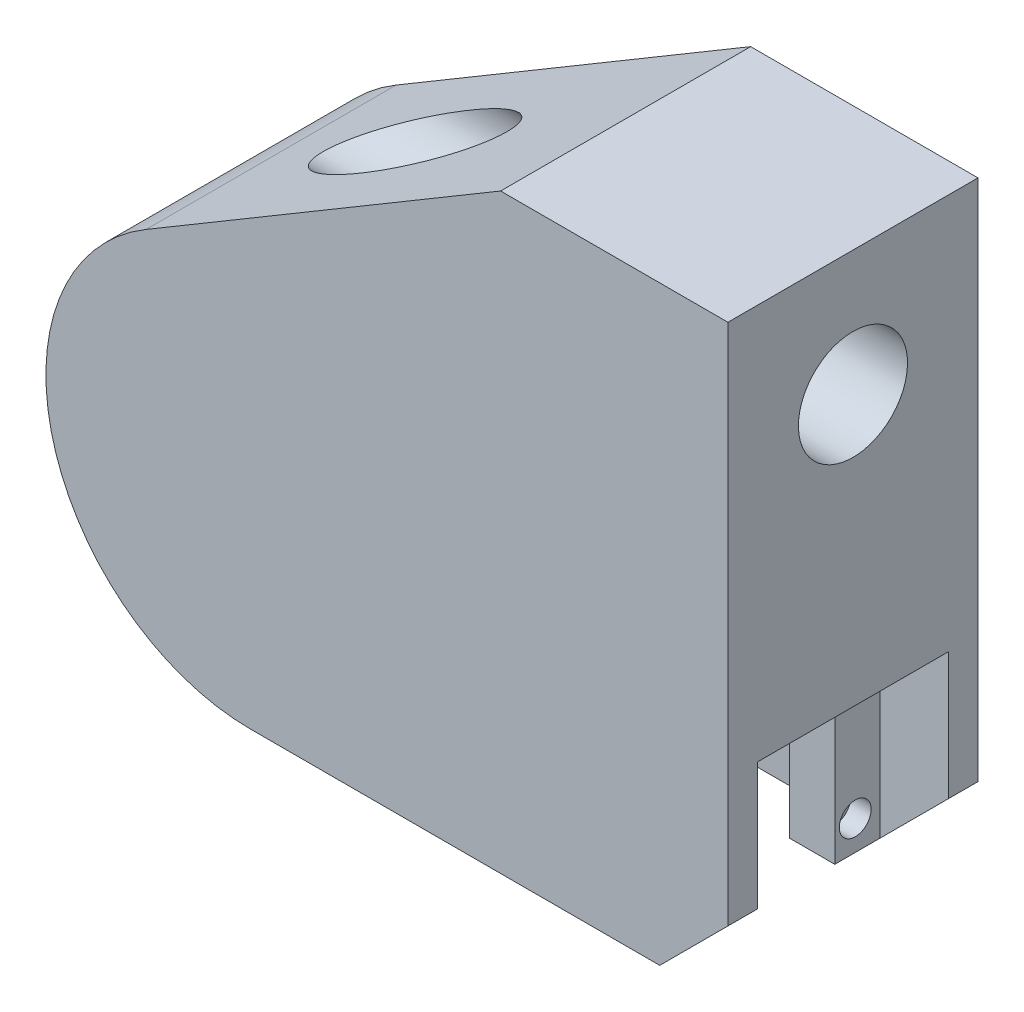
SolidWorks part; units mm, degrees
ref_plane "Ebene vorne" through (0, 0, 0) normal (0, 0, 1) x (1, 0, 0)
ref_plane "Ebene oben" through (0, 0, 0) normal (0, 1, 0) x (1, 0, 0)
ref_plane "Ebene rechts" through (0, 0, 0) normal (1, 0, 0) x (0, 0, -1)
sketch "Skizze1" plane through (0, 0, 0) normal (0, 0, 1) x (1, 0, 0)
  line L0 (55, 85) -> (-22.9777, 38.6914)
  line L1 (105, 85) -> (55, 85)
  line L2 (105, 85) -> (105, 35)
  line L3 (105, 35) -> (55, 35)
  line L4 (55, 85) -> (55, 35)
  line L5 (105, 85) -> (55, 35) construction
  line L6 (105, 35) -> (55, 85) construction
  line L7 (105, 35) -> (105, -45)
  line L8 (105, -45) -> (0, -45)
  circle A0 centre (0, 0) radius 45
  point P3 (80, 60)
  dimension "D1" = 90
  dimension "D2" = 50
  dimension "D3" = 50
  dimension "D4" = 80
  dimension "D5" = 60
extrude "Aufsatz-Linear austragen2" add sketch "Skizze1" along normal blind 55 contours A0 L8 L7 L3 L4 L0 | L1 L4 L3 L2 | A0 region at (61.5827, 8.2985, 0) region at (80, 60, 0) region at (0, 0, 0)
sketch "Skizze3" plane through (0, -45, 0) normal (0, -1, 0) x (1, 0, 0)
  line L0 (19, 55) -> (19, 0)
  line L1 (90, 55) -> (19, 55)
  line L2 (90, 55) -> (90, 48.5)
  line L3 (90, 48.5) -> (19, 48.5)
  line L4 (19, 55) -> (19, 48.5)
  line L5 (90, 55) -> (19, 48.5) construction
  line L6 (90, 48.5) -> (19, 55) construction
  line L7 (105, 48.5) -> (105, 6.5)
  line L8 (90, 48.5) -> (80, 48.5)
  line L9 (90, 48.5) -> (90, 38.5)
  line L10 (90, 38.5) -> (80, 38.5)
  line L11 (80, 48.5) -> (80, 38.5)
  line L12 (90, 48.5) -> (80, 38.5) construction
  line L13 (90, 38.5) -> (80, 48.5) construction
  line L14 (90, 0) -> (19, 0)
  line L15 (90, 0) -> (90, 6.5)
  line L16 (90, 6.5) -> (19, 6.5)
  line L17 (19, 0) -> (19, 6.5)
  line L18 (90, 0) -> (19, 6.5) construction
  line L19 (90, 6.5) -> (19, 0) construction
  line L20 (90, 6.5) -> (80, 6.5)
  line L21 (90, 6.5) -> (90, 16.5)
  line L22 (90, 16.5) -> (80, 16.5)
  line L23 (80, 6.5) -> (80, 16.5)
  line L24 (90, 6.5) -> (80, 16.5) construction
  line L25 (90, 16.5) -> (80, 6.5) construction
  line L26 (105, 55) -> (105, 0) construction
  line L28 (90, 55) -> (105, 55)
  line L29 (90, 55) -> (90, 48.5)
  line L30 (90, 48.5) -> (105, 48.5)
  line L31 (105, 55) -> (105, 48.5)
  line L32 (90, 55) -> (105, 48.5) construction
  line L33 (90, 48.5) -> (105, 55) construction
  line L34 (90, 0) -> (105, 0)
  line L35 (90, 0) -> (90, 6.5)
  line L36 (90, 6.5) -> (105, 6.5)
  line L37 (105, 0) -> (105, 6.5)
  line L38 (90, 0) -> (105, 6.5) construction
  line L39 (90, 6.5) -> (105, 0) construction
  point P4 (54.5, 51.75)
  point P11 (85, 43.5)
  point P16 (54.5, 3.25)
  point P21 (85, 11.5)
  point P25 (97.5, 51.75)
  point P27 (97.5, 3.25)
  line M7 (105, 0) -> (105, 55)
  dimension "D1" = 42
  dimension "D2" = 6.5
  dimension "D3" = 22
  dimension "D4" = 10
  dimension "D5" = 10
  dimension "D6" = 61
  dimension "D7" = 15
extrude "Schnitt-Linear austragen1" cut sketch "Skizze3" against normal blind 43 contours L16 L23 L22 L10 L11 L3 L0 M7 region at (60.6518, -45, 27.5)
sketch "Skizze4" plane through (90, 0, 0) normal (1, 0, 0) x (0, 0, -1)
  line L0 (-38.5, -2) -> (-48.5, -2) construction
  line L3 (-48.5, -2) -> (-6.5, -2)
  line L4 (-48.5, -2) -> (-48.5, -44)
  line L5 (-48.5, -44) -> (-6.5, -44)
  line L6 (-6.5, -2) -> (-6.5, -44)
  line L7 (-48.5, -2) -> (-44.0604, -6.4396) construction
  line L8 (-48.5, -44) -> (-6.5, -2) construction
  line L9 (-55, -45) -> (-48.5, -45) construction
  line L10 (-41.9391, -8.5609) -> (-6.5, -44) construction
  arc A0 (-44.0235, -8.5965) -> (-13.0965, -39.5235) centre (-27.5, -23) ccw
  circle A1 centre (-12.0002, -7.5002) radius 1.5
  circle A2 centre (-12.0002, -38.4998) radius 1.5
  circle A3 centre (-42.9998, -38.4998) radius 1.5
  circle A4 centre (-42.9998, -7.5002) radius 1.5
  arc A5 (-13.0965, -6.4765) -> (-41.9035, -6.4765) centre (-27.5, -23) ccw
  arc A6 (-10.9765, -37.4035) -> (-10.9765, -8.5965) centre (-27.5, -23) ccw
  point P8 (-27.5, -23)
  point P23 (-27.5, -23)
  dimension "D4" = 4
  dimension "D5" = 3
  dimension "D1" = 1
  dimension "D2" = 27.5
  dimension "D3" = 42
extrude "Schnitt-Linear austragen2" cut sketch "Skizze4" against normal blind 10 contours A4 | A1 | A2 | A0 A3 | A0 A3 region at (90, -7.5002, 42.9998) region at (90, -7.5002, 12.0002) region at (90, -38.0431, 42.5431) region at (90, -38.9433, 43.4433) region at (90, -38.4998, 12.0002)
sketch "Skizze5" plane through (90, 0, 0) normal (1, 0, 0) x (0, 0, -1)
  circle A0 centre (-42.9998, -7.5002) radius 3.5
  circle A1 centre (-12.0002, -7.5002) radius 3.5
  circle A2 centre (-12.0002, -38.4998) radius 3.5
  circle A3 centre (-42.9998, -38.4998) radius 3.5
  dimension "D1" = 7
extrude "Schnitt-Linear austragen3" cut sketch "Skizze5" against normal blind 4.5
ref_plane "Ebene1" through (0, 0, 27.5) normal (0, 0, 1) x (1, 0, 0)
sketch "Skizze6" plane through (0, 0, 27.5) normal (0, 0, 1) x (1, 0, 0)
  line L0 (19, 10) -> (0, 10)
  line L1 (105, -45) -> (80, -45)
  line L2 (105, -45) -> (105, -2)
  line L3 (105, -2) -> (80, -2)
  line L4 (80, -45) -> (80, -2)
  line L5 (105, -45) -> (80, -2) construction
  line L6 (105, -2) -> (80, -45) construction
  line L7 (80, -45) -> (19, -45)
  line L8 (80, -45) -> (80, -2)
  line L9 (80, -2) -> (19, -2)
  line L10 (19, -45) -> (19, -2)
  line L11 (80, -45) -> (19, -2) construction
  line L12 (80, -2) -> (19, -45) construction
  line L13 (19, -2) -> (29, -2)
  line L14 (19, -2) -> (19, 10)
  line L15 (19, 10) -> (29, 10)
  line L16 (29, -2) -> (29, 10)
  line L17 (19, -2) -> (29, 10) construction
  line L18 (19, 10) -> (29, -2) construction
  line L19 (19, 2.5) -> (9.6825, 2.5)
  circle A1 centre (0, 0) radius 10
  point P7 (92.5, -23.5)
  point P11 (49.5, -23.5)
  point P15 (24, 4)
  dimension "D1" = 43
  dimension "D6" = 7.5
  dimension "D2" = 25
  dimension "D3" = 61
  dimension "D4" = 10
  dimension "D5" = 12
extrude "Schnitt-Linear austragen4" cut sketch "Skizze6" along normal mid plane 14 contours L9 L16 L15 L14 | A1 L14 L0 region at (12.8844, 6.6298, 27.5) region at (24, 4, 27.5)
sketch "Skizze7" plane through (0, 0, 55) normal (0, 0, 1) x (1, 0, 0)
  circle A0 centre (0, 0) radius 10
  dimension "D1" = 20
extrude "Schnitt-Linear austragen5" cut sketch "Skizze7" against normal blind 49 from offset 6 offset against normal yes
sketch "Skizze8" plane through (105, 0, 0) normal (1, 0, 0) x (0, 0, -1)
  line L0 (-55, 85) -> (-55, -45) construction
  line L1 (-55, 85) -> (0, 85) construction
  line L2 (0, 85) -> (0, -45) construction
  circle A0 centre (-27.5, 57.5) radius 27.5
  circle A1 centre (-27.5, 57.5) radius 12
extrude "Schnitt-Linear austragen6" cut sketch "Skizze8" against normal through all contours A1
sketch "Skizze9" plane through (0, 0, 0) normal (0, 0, -1) x (-1, 0, 0)
  line L0 (0, 0) -> (-3.3743, 14.6156) construction
  circle A5 centre (0, 0) radius 15
  circle A6 centre (-3.3743, 14.6156) radius 1.65
  circle A7 centre (14.6156, 3.3743) radius 1.65
  circle A8 centre (3.3743, -14.6156) radius 1.65
  circle A9 centre (-14.6156, -3.3743) radius 1.65
  point P13 (0, 0)
  dimension "D1" = 30
extrude "Schnitt-Linear austragen9" cut sketch "Skizze9" against normal blind 20 contours A5 A6 | A6 L0 A5 | L0 A6 A5 | A5 A7 | A5 A7 | A5 A9 | A5 A9 | A5 A8 | A5 A8 region at (3.8829, 13.7629, 0) region at (2.5433, 14.0722, 0) region at (3.5281, 15.2817, 0) region at (13.9175, -3.2131, 0) region at (15.2817, -3.5281, 0) region at (-15.2817, 3.5281, 0) region at (-13.9175, 3.2131, 0) region at (-3.2131, -13.9175, 0) region at (-3.5281, -15.2817, 0)
chamfer "Fase1" distance 15 angle 45 2 edges at (105, -45, 51.75) (105, -45, 3.25)
